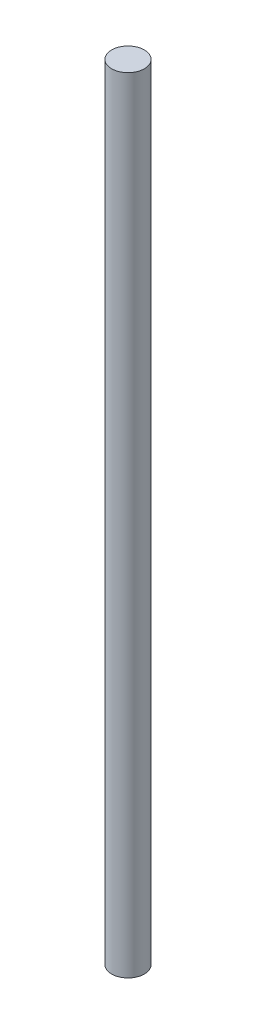
SolidWorks part; units mm, degrees
ref_plane "Front Plane" through (0, 0, 0) normal (0, 0, 1) x (1, 0, 0)
ref_plane "Top Plane" through (0, 0, 0) normal (0, 1, 0) x (1, 0, 0)
ref_plane "Right Plane" through (0, 0, 0) normal (1, 0, 0) x (0, 0, -1)
sketch "Sketch1" plane through (0, 0, 0) normal (0, 1, 0) x (1, 0, 0)
  circle A0 centre (0, 0) radius 12.7
extrude "Boss-Extrude1" add sketch "Sketch1" along normal blind 609.6
